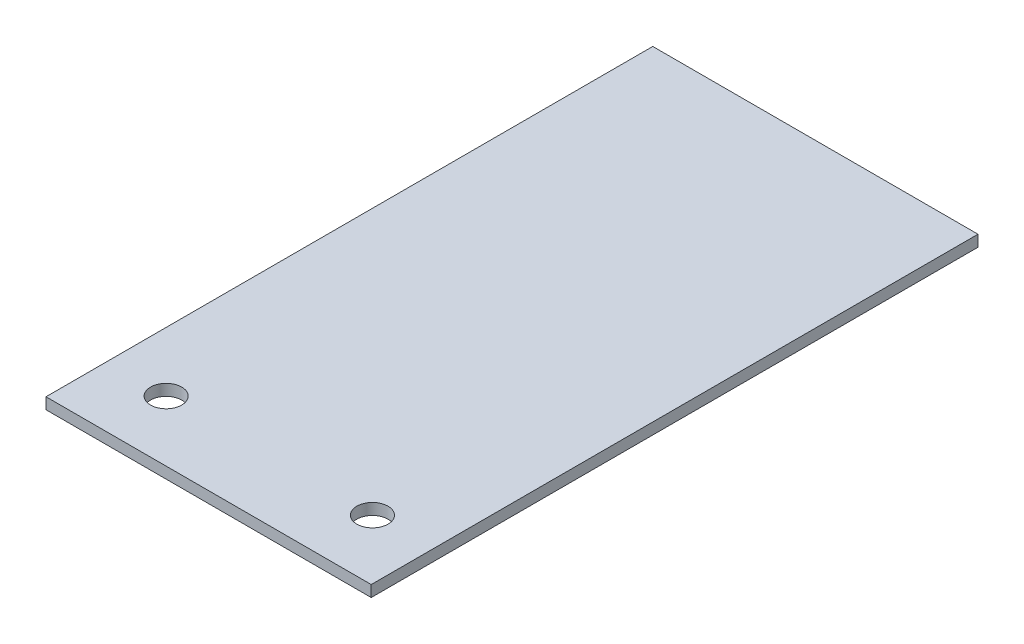
SolidWorks part; units mm, degrees
ref_plane "Front Plane" through (0, 0, 0) normal (0, 0, 1) x (1, 0, 0)
ref_plane "Top Plane" through (0, 0, 0) normal (0, 1, 0) x (1, 0, 0)
ref_plane "Right Plane" through (0, 0, 0) normal (1, 0, 0) x (0, 0, -1)
sketch "Sketch1" plane through (0, 0, 0) normal (0, 1, 0) x (1, 0, 0)
  line L1 (0, 0) -> (-68.072, 0)
  line L2 (0, 0) -> (0, 127)
  line L3 (0, 127) -> (-68.072, 127)
  line L4 (-68.072, 0) -> (-68.072, 127)
  dimension "D1" = 127
  dimension "D2" = 68.072
extrude "Boss-Extrude1" add sketch "Sketch1" along normal blind 2.3622
sketch "Sketch2" plane through (0, 2.3622, 0) normal (0, 1, 0) x (1, 0, 0)
  line L0 (-68.072, 0) -> (0, 0) construction
  circle A0 centre (-55.626, 12.7) radius 3.2639
  circle A1 centre (-12.446, 12.7) radius 3.2639
  point P7 (-34.036, 0)
  dimension "D1" = 6.5278
  dimension "D2" = 12.7
  dimension "D3" = 43.18
  dimension "D4" = 21.59
extrude "Cut-Extrude1" cut sketch "Sketch2" against normal through all
